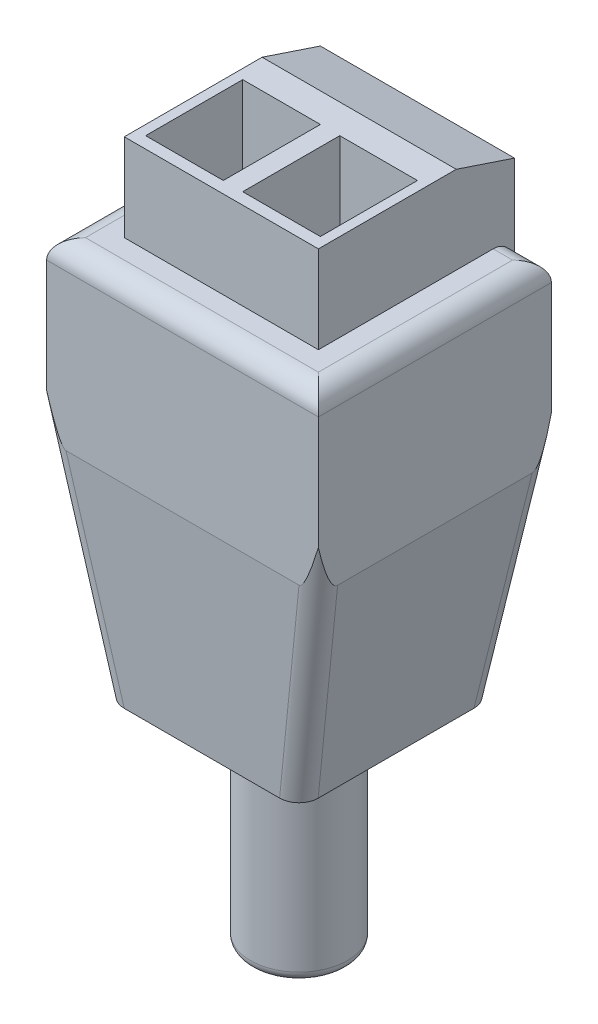
SolidWorks part; units mm, degrees
ref_plane "Front" through (0, 0, 0) normal (0, 0, 1) x (1, 0, 0)
ref_plane "Top" through (0, 0, 0) normal (0, 1, 0) x (1, 0, 0)
ref_plane "Right" through (0, 0, 0) normal (1, 0, 0) x (0, 0, -1)
sketch "草图1" plane through (0, 0, 0) normal (0, 1, 0) x (1, 0, 0)
  line L1 (0, 0) -> (14, 0)
  line L2 (0, 0) -> (0, 12)
  line L3 (0, 12) -> (14, 12)
  line L4 (14, 0) -> (14, 12)
  dimension "D1" = 14
  dimension "D2" = 12
extrude "凸台-拉伸1" add sketch "草图1" along normal blind 9
fillet "圆角2" radius 1 4 edges at (7, 9, -12) (14, 9, -6) (7, 9, 0) (0, 9, -6)
sketch "草图4" plane through (0, 0, 0) normal (0, -1, 0) x (1, 0, 0)
  line L1 (0, 0) -> (14, 0)
  line L2 (0, 0) -> (0, -12)
  line L3 (0, -12) -> (14, -12)
  line L4 (14, 0) -> (14, -12)
ref_plane "基准面2" through (0, -11, 0) normal (0, -1, 0) x (-1, 0, 0)
sketch "草图5" plane through (0, -11, 0) normal (0, -1, 0) x (-1, 0, 0)
  line L0 (0, 0) -> (-14, 0) construction
  line L1 (-2, 1) -> (-12, 1)
  line L2 (-2, 1) -> (-2, 11)
  line L3 (-2, 11) -> (-12, 11)
  line L4 (-12, 1) -> (-12, 11)
  line L5 (-14, 0) -> (-14, 12) construction
  dimension "D1" = 10
  dimension "D2" = 10
  dimension "D3" = 1
  dimension "D4" = 2
loft "放样1" add profiles "草图4", "草图5" connector at (14, 0, 0) connector at (12, -11, -1)
fillet "圆角3" radius 1 4 edges
sketch "草图6" plane through (0, -11, 0) normal (0, -1, 0) x (1, 0, 0)
  circle A0 centre (7, -6) radius 2.5
extrude "凸台-拉伸2" add sketch "草图6" along normal blind 11
fillet "圆角4" radius 0.5 1 edges at (7, -22, -8.5)
sketch "草图7" plane through (0, -22, 0) normal (0, -1, 0) x (1, 0, 0)
  circle A0 centre (7, -6) radius 2
extrude "切除-拉伸1" cut sketch "草图7" against normal blind 0.5
fillet "圆角5" radius 0.5 1 edges at (7, -21.5, -8)
sketch "草图8" plane through (0, 0, -12) normal (0, 0, -1) x (-1, 0, 0)
  line L0 (-13, 9) -> (-1, 9) construction
  line L1 (-2, 7.5) -> (-12, 7.5)
  line L2 (-2, 7.5) -> (-2, 13.1076)
  line L3 (-2, 13.1076) -> (-12, 13.1076)
  line L4 (-12, 7.5) -> (-12, 13.1076)
  point P6 (-7, 7.5)
  point P7 (-7, 9)
  dimension "D1" = 10
  dimension "D2" = 1.5
  dimension "D3" = 0
extrude "切除-拉伸2" cut sketch "草图8" against normal blind 10
sketch "草图9" plane through (0, 0, -2) normal (0, 0, -1) x (-1, 0, 0)
  line L1 (-12, 7.5) -> (-2, 7.5)
  line L2 (-12, 7.5) -> (-12, 13.5)
  line L3 (-12, 13.5) -> (-2, 13.5)
  line L4 (-2, 7.5) -> (-2, 13.5)
  dimension "D1" = 6
extrude "凸台-拉伸3" add sketch "草图9" along normal blind 10.1
sketch "草图10" plane through (0, 0, -12.1) normal (0, 0, -1) x (-1, 0, 0)
  line L0 (-2, 7.5) -> (-2, 13.5) construction
  line L1 (-12, 13.5) -> (-12, 7.5) construction
  line L2 (-12, 7.5) -> (-2, 7.5) construction
  line L3 (-12, 7.5) -> (-2, 7.5) construction
  circle A0 centre (-4.5, 10) radius 1.75
  circle A1 centre (-9.5, 10) radius 1.75
  dimension "D1" = 2.5
  dimension "D2" = 2.5
  dimension "D3" = 2.5
  dimension "D4" = 2.5
extrude "切除-拉伸3" cut sketch "草图10" against normal blind 0.5
sketch "草图11" plane through (2, 0, 0) normal (-1, 0, 0) x (0, 0, 1)
  line L0 (-12.1, 12.5) -> (-12.1, 13.5)
  line L1 (-12.1, 7.5) -> (-12.1, 13.5) construction
  line L2 (-12.1, 13.5) -> (-9.1, 13.5)
  line L3 (-12.1, 13.5) -> (-2, 13.5) construction
  line L4 (-9.1, 13.5) -> (-12.1, 12.5)
  dimension "D1" = 1
  dimension "D2" = 3
extrude "切除-拉伸4" cut sketch "草图11" against normal through all
sketch "草图12" plane through (0, 13.5, 0) normal (0, 1, 0) x (1, 0, 0)
  line L0 (2, 2) -> (2, 11) construction
  line L1 (2.5, 7.6) -> (6.5, 7.6)
  line L2 (2.5, 7.6) -> (2.5, 2.6)
  line L3 (2.5, 2.6) -> (6.5, 2.6)
  line L4 (6.5, 7.6) -> (6.5, 2.6)
  line L5 (2, 2) -> (12, 2) construction
  line L6 (12, 9.1) -> (12, 2) construction
  line L7 (7.5, 7.6) -> (11.5, 7.6)
  line L8 (7.5, 7.6) -> (7.5, 2.6)
  line L9 (7.5, 2.6) -> (11.5, 2.6)
  line L10 (11.5, 7.6) -> (11.5, 2.6)
  dimension "D1" = 4
  dimension "D2" = 5
  dimension "D3" = 0.5
  dimension "D4" = 0.6
  dimension "D5" = 4
  dimension "D6" = 0.5
extrude "切除-拉伸5" cut sketch "草图12" against normal blind 5
